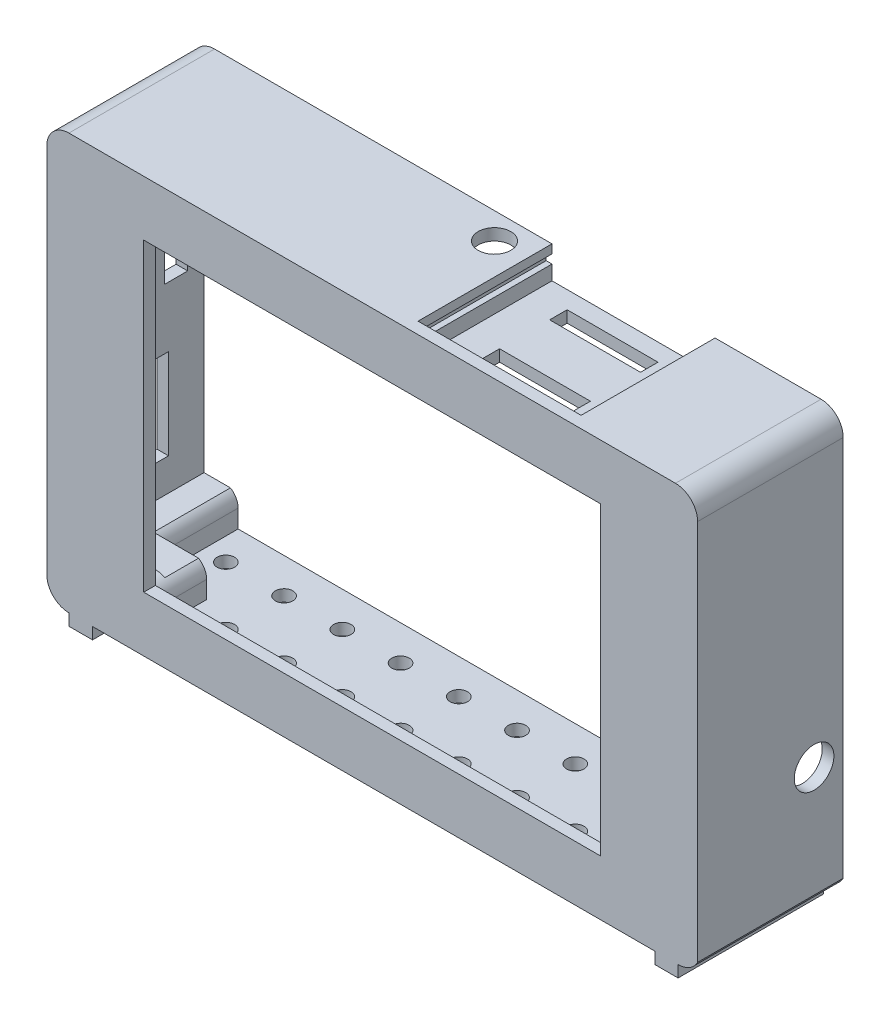
SolidWorks part; units mm, degrees
ref_plane "Спереди" through (0, 0, 0) normal (0, 0, 1) x (1, 0, 0)
ref_plane "Сверху" through (0, 0, 0) normal (0, 1, 0) x (1, 0, 0)
ref_plane "Справа" through (0, 0, 0) normal (1, 0, 0) x (0, 0, -1)
sketch "Skizze2" plane through (0, 0, 0) normal (0, 0, 1) x (1, 0, 0)
  line L12 (26.3261, 18.4704) -> (26.3261, 24.5704)
  line L13 (11.7261, 12.5004) -> (11.7261, 26.2004)
  line L14 (-51.1739, -27.8496) -> (45.3261, -27.8496)
  line L15 (-52.0078, 10.838) -> (-53.3578, 10.838)
  line L20 (-52.0078, 3.4844) -> (-53.3578, 3.4844)
  line L21 (-53.3578, 3.4844) -> (-53.3578, 3.338)
  line L22 (-53.3578, 3.338) -> (-52.0078, 3.338)
  line L23 (-52.0078, 3.338) -> (-52.0078, 3.4844)
  line L24 (-53.1739, 25.0904) -> (-53.1739, -25.8496)
  line L25 (45.3261, 27.0904) -> (-51.1739, 27.0904)
  line L26 (47.3261, -25.8496) -> (47.3261, 25.0904)
  line L27 (-39.7339, -26.5596) -> (38.7061, -26.5596)
  line L28 (-39.7339, 12.4004) -> (-39.7339, -26.5596)
  line L29 (38.7061, 25.8004) -> (-41.7339, 25.8004)
  line L30 (38.7061, -26.5596) -> (38.7061, 25.8004)
  circle A8 centre (44.1261, -24.6496) radius 1.6
  arc A9 (45.3261, -27.8496) -> (47.3261, -25.8496) centre (45.3261, -25.8496) ccw
  arc A10 (-53.1739, -25.8496) -> (-51.1739, -27.8496) centre (-51.1739, -25.8496) ccw
  circle A11 centre (-49.9739, -24.6496) radius 1.6
  arc A12 (-51.1739, 27.0904) -> (-53.1739, 25.0904) centre (-51.1739, 25.0904) ccw
  circle A13 centre (-49.9739, 23.8904) radius 1.6
  circle A14 centre (44.1261, 23.8904) radius 1.6
  arc A15 (47.3261, 25.0904) -> (45.3261, 27.0904) centre (45.3261, 25.0904) ccw
sketch "Skizze3" plane through (0, 0, 0) normal (0, 0, 1) x (1, 0, 0)
  line L0 (38.7061, -26.5596) -> (38.7061, 25.8004) construction
  line L1 (-39.7339, -26.5596) -> (38.7061, -26.5596) construction
  line L2 (-39.7339, 12.4004) -> (-39.7339, -26.5596) construction
  line L3 (38.7061, -26.5596) -> (38.7061, 25.8004)
  line L4 (-39.7339, -26.5596) -> (38.7061, -26.5596)
  line L5 (-39.7339, 12.4004) -> (-39.7339, -26.5596)
  line L6 (38.7061, 25.8004) -> (-39.7339, 25.8004)
  line L7 (38.7061, 25.8004) -> (-41.7339, 25.8004) construction
  line L8 (-39.7339, 25.8004) -> (-39.7339, 12.4004)
  line L9 (45.3261, 27.0904) -> (-51.1739, 27.0904) construction
  line L10 (-54.3739, 33.2904) -> (48.5261, 33.2904)
  line L11 (-54.3739, 33.2904) -> (-54.3739, -34.0496)
  line L12 (-54.3739, -34.0496) -> (48.5261, -34.0496)
  line L13 (48.5261, 33.2904) -> (48.5261, -34.0496)
  line L14 (-53.1739, 25.0904) -> (-53.1739, -25.8496) construction
  line L15 (47.3261, -25.8496) -> (47.3261, 25.0904) construction
  line L16 (-51.1739, -27.8496) -> (45.3261, -27.8496) construction
  circle A0 centre (-49.9739, 23.8904) radius 1.6 construction
  circle A1 centre (-49.9739, -24.6496) radius 1.6 construction
  circle A2 centre (44.1261, -24.6496) radius 1.6 construction
  circle A3 centre (44.1261, 23.8904) radius 1.6 construction
  circle A4 centre (-49.9739, 23.8904) radius 1.6
  circle A5 centre (-49.9739, -24.6496) radius 1.6
  circle A6 centre (44.1261, -24.6496) radius 1.6
  circle A7 centre (44.1261, 23.8904) radius 1.6
  dimension "D1" = 6.2
  dimension "D2" = 1.2
  dimension "D3" = 1.2
  dimension "D4" = 6.2
extrude "Aufsatz-Linear austragen1" add sketch "Skizze3" along normal blind 2
sketch "Skizze4" plane through (0, 0, 2) normal (0, 0, 1) x (1, 0, 0)
  line L1 (48.5261, 33.2904) -> (53.3661, 33.2904)
  line L2 (48.5261, 33.2904) -> (48.5261, -29.0496)
  line L3 (48.5261, -29.0496) -> (53.3661, -29.0496)
  line L4 (53.3661, 33.2904) -> (53.3661, -29.0496)
  dimension "D1" = 4.84
extrude "Aufsatz-Linear austragen2" add sketch "Skizze4" against normal blind 2
sketch "Skizze5" plane through (0, 0, 0) normal (0, 0, -1) x (-1, 0, 0)
  circle A0 centre (-44.1261, 23.8904) radius 1.6 construction
  circle A1 centre (-44.1261, -24.6496) radius 1.6 construction
  circle A2 centre (49.9739, -24.6496) radius 1.6 construction
  circle A3 centre (49.9739, 23.8904) radius 1.6 construction
  circle A4 centre (-44.1261, 23.8904) radius 1.6
  circle A5 centre (-44.1261, -24.6496) radius 1.6
  circle A6 centre (49.9739, -24.6496) radius 1.6
  circle A7 centre (49.9739, 23.8904) radius 1.6
extrude "Linear-Austragen-Dünn1" add sketch "Skizze5" along normal blind 4 thin thin type one direction wall 1.8
sketch "Skizze6" plane through (53.3661, 0, 0) normal (1, 0, 0) x (0, 0, -1)
  line L0 (0, -29.0496) -> (-2, -29.0496) construction
  line L1 (-2, 33.2904) -> (23, 33.2904)
  line L2 (-2, 33.2904) -> (-2, -29.0496)
  line L3 (-2, -29.0496) -> (23, -29.0496)
  line L4 (23, 33.2904) -> (23, -29.0496)
  dimension "D1" = 25
extrude "Aufsatz-Linear austragen3" add sketch "Skizze6" along normal blind 2
sketch "Skizze7" plane through (-54.3739, 0, 0) normal (-1, 0, 0) x (0, 0, 1)
  line L0 (2, 33.2904) -> (0, 33.2904) construction
  line L1 (2, -34.0496) -> (-23, -34.0496)
  line L2 (2, -34.0496) -> (2, 33.2904)
  line L3 (2, 33.2904) -> (-23, 33.2904)
  line L4 (-23, -34.0496) -> (-23, 33.2904)
  dimension "D1" = 25
extrude "Aufsatz-Linear austragen4" add sketch "Skizze7" along normal blind 2
sketch "Skizze8" plane through (0, 33.2904, 0) normal (0, 1, 0) x (1, 0, 0)
  line L1 (-56.3739, -2) -> (55.3661, -2)
  line L2 (-56.3739, -2) -> (-56.3739, 23)
  line L3 (-56.3739, 23) -> (55.3661, 23)
  line L4 (55.3661, -2) -> (55.3661, 23)
extrude "Aufsatz-Linear austragen5" add sketch "Skizze8" along normal blind 2
sketch "Skizze9" plane through (0, -34.0496, 0) normal (0, -1, 0) x (1, 0, 0)
  line L1 (55.3661, 2) -> (-56.3739, 2)
  line L2 (55.3661, 2) -> (55.3661, -23)
  line L3 (55.3661, -23) -> (-56.3739, -23)
  line L4 (-56.3739, 2) -> (-56.3739, -23)
extrude "Aufsatz-Linear austragen6" add sketch "Skizze9" along normal blind 2
fillet "Verrundung2" radius 3.8 4 edges at (55.3661, 35.2904, -10.5) (55.3661, -36.0496, -10.5) (-56.3739, -36.0496, -10.5) (-56.3739, 35.2904, -10.5)
sketch "Skizze10" plane through (-56.3739, 0, 0) normal (-1, 0, 0) x (0, 0, 1)
  line L0 (-23, 35.2904) -> (2, 35.2904) construction
  line L1 (-20.2, 11.7904) -> (-16.2, 11.7904)
  line L2 (-20.2, 11.7904) -> (-20.2, 2.7904)
  line L3 (-20.2, 2.7904) -> (-16.2, 2.7904)
  line L4 (-16.2, 11.7904) -> (-16.2, 2.7904)
  line L5 (-23, -29.0496) -> (-23, 33.2904) construction
  line L6 (-23, 31.4904) -> (-23, -32.2496) construction
  line L7 (-16.4, -8.5496) -> (-12.9, -8.5496)
  line L8 (-16.4, -8.5496) -> (-16.4, -22.0496)
  line L9 (-16.4, -22.0496) -> (-12.9, -22.0496)
  line L10 (-12.9, -8.5496) -> (-12.9, -22.0496)
  line L11 (2, -36.0496) -> (-23, -36.0496) construction
  dimension "D1" = 9
  dimension "D2" = 4
  dimension "D3" = 23.5
  dimension "D4" = 2.8
  dimension "D5" = 3.5
  dimension "D6" = 13.5
  dimension "D7" = 6.6
  dimension "D8" = 14
extrude "Schnitt-Linear austragen1" cut sketch "Skizze10" against normal blind 10
sketch "Skizze23" plane through (0, 0, 0) normal (0, 0, -1) x (-1, 0, 0)
  line L0 (-53.3661, 33.2904) -> (54.3739, 33.2904) construction
  line L1 (-33.3661, 33.2904) -> (-35.3661, 33.2904)
  line L2 (-33.3661, 33.2904) -> (-33.3661, 27.7904)
  line L3 (-33.3661, 27.7904) -> (-35.3661, 27.7904)
  line L4 (-35.3661, 33.2904) -> (-35.3661, 27.7904)
  line L5 (-55.3661, -29.0496) -> (-55.3661, 31.4904) construction
  line L6 (-3.3661, 33.2904) -> (-5.3661, 33.2904)
  line L7 (-3.3661, 33.2904) -> (-3.3661, 27.7904)
  line L8 (-3.3661, 27.7904) -> (-5.3661, 27.7904)
  line L9 (-5.3661, 33.2904) -> (-5.3661, 27.7904)
  line L10 (-33.3661, 27.7904) -> (-5.3661, 27.7904)
  line L11 (-33.3661, 27.7904) -> (-33.3661, 29.7904)
  line L12 (-33.3661, 29.7904) -> (-5.3661, 29.7904)
  line L13 (-5.3661, 27.7904) -> (-5.3661, 29.7904)
  line L14 (-45.3261, 27.0904) -> (51.1739, 27.0904) construction
  line M14 (54.3739, 33.2904) -> (-53.3661, 33.2904)
  dimension "D1" = 2
  dimension "D2" = 2
  dimension "D3" = 2
  dimension "D4" = 20
  dimension "D5" = 28
  dimension "D6" = 0.7
extrude "Aufsatz-Linear austragen13" add sketch "Skizze23" along normal blind 23 contours L12 L2 L10 L9 | L9 L8 L7 M14 | L4 L3 L2 M14 region at (34.3661, 30.5404, 0) region at (19.3661, 28.7904, 0) region at (4.3661, 30.5404, 0)
sketch "Skizze11" plane through (0, 35.2904, 0) normal (0, 1, 0) x (1, 0, 0)
  line L0 (45.3261, 0) -> (-51.1739, 0) construction
  line L1 (10.9661, 8.4) -> (26.5661, 8.4)
  line L2 (10.9661, 8.4) -> (10.9661, 5.4)
  line L3 (10.9661, 5.4) -> (26.5661, 5.4)
  line L4 (26.5661, 8.4) -> (26.5661, 5.4)
  line L5 (10.9661, 20) -> (26.5661, 20)
  line L6 (10.9661, 20) -> (10.9661, 17)
  line L7 (10.9661, 17) -> (26.5661, 17)
  line L8 (26.5661, 20) -> (26.5661, 17)
  line L10 (55.3661, 23) -> (55.3661, -2) construction
  dimension "D1" = 3
  dimension "D2" = 3
  dimension "D4" = 15.6
  dimension "D5" = 5.4
  dimension "D6" = 8.6
  dimension "D7" = 28.8
extrude "Schnitt-Linear austragen2" cut sketch "Skizze11" against normal blind 10
fillet "Verrundung3" radius 1 8 edges at (10.9661, 35.2904, -6.9) (18.7661, 35.2904, -8.4) (26.5661, 35.2904, -6.9) (10.9661, 35.2904, -18.5) (26.5661, 35.2904, -18.5) (18.7661, 35.2904, -20) (18.7661, 35.2904, -17) (18.7661, 35.2904, -5.4)
sketch "Skizze14" plane through (0, -36.0496, 0) normal (0, -1, 0) x (1, 0, 0)
  line L0 (55.3661, 2) -> (55.3661, -23) construction
  line L1 (-52.5739, -23) -> (52.0195, -23) construction
  circle A0 centre (45.3661, -17) radius 1.5
  circle A1 centre (35.3661, -17) radius 1.5
  circle A2 centre (25.3661, -17) radius 1.5
  circle A3 centre (15.3661, -17) radius 1.5
  circle A4 centre (5.3661, -17) radius 1.5
  circle A5 centre (-4.6339, -17) radius 1.5
  circle A6 centre (-14.6339, -17) radius 1.5
  circle A7 centre (-24.6339, -17) radius 1.5
  circle A8 centre (-34.6339, -17) radius 1.5
  circle A9 centre (-44.6339, -17) radius 1.5
  circle A10 centre (35.3661, -7) radius 1.5
  circle A11 centre (25.3661, -7) radius 1.5
  circle A12 centre (15.3661, -7) radius 1.5
  circle A13 centre (5.3661, -7) radius 1.5
  circle A14 centre (-4.6339, -7) radius 1.5
  circle A15 centre (-14.6339, -7) radius 1.5
  circle A16 centre (-24.6339, -7) radius 1.5
  circle A17 centre (-34.6339, -7) radius 1.5
  circle A18 centre (-44.6339, -7) radius 1.5
  circle A19 centre (45.3661, -7) radius 1.5
  dimension "D1" = 3
  dimension "D2" = 10
  dimension "D3" = 6
  dimension "D4" = 10
  dimension "D5" = 2
extrude "Schnitt-Linear austragen4" cut sketch "Skizze14" against normal blind 10
sketch "Skizze15" plane through (53.3661, 0, 0) normal (-1, 0, 0) x (0, 0, 1)
  line L1 (-23, -29.0496) -> (-23, 33.2904) construction
  line L2 (-23, -34.0496) -> (2, -34.0496) construction
  circle A0 centre (-18, -15.0496) radius 3.4
  dimension "D1" = 6.8
  dimension "D2" = 19
  dimension "D3" = 5
extrude "Schnitt-Linear austragen5" cut sketch "Skizze15" against normal blind 10
sketch "Skizze16" plane through (0, 0, 2) normal (0, 0, 1) x (1, 0, 0)
  circle A0 centre (44.1261, 23.8904) radius 1.6 construction
  circle A1 centre (44.1261, -24.6496) radius 1.6 construction
  circle A2 centre (-49.9739, -24.6496) radius 1.6 construction
  circle A3 centre (-49.9739, 23.8904) radius 1.6 construction
  circle A4 centre (44.1261, 23.8904) radius 1.6
  circle A5 centre (44.1261, -24.6496) radius 1.6
  circle A6 centre (-49.9739, -24.6496) radius 1.6
  circle A7 centre (-49.9739, 23.8904) radius 1.6
extrude "Aufsatz-Linear austragen7" add sketch "Skizze16" against normal blind 6
sketch "Skizze17" plane through (0, 0, -4) normal (0, 0, -1) x (-1, 0, 0)
  circle A0 centre (-44.1261, 23.8904) radius 1.05
  circle A1 centre (49.9739, 23.8904) radius 1.05
  circle A2 centre (49.9739, -24.6496) radius 1.05
  circle A3 centre (-44.1261, -24.6496) radius 1.05
  dimension "D1" = 2.1
extrude "Schnitt-Linear austragen6" cut sketch "Skizze17" against normal blind 5
fillet "Verrundung4" radius 2 2 edges at (-54.3739, 33.2904, -11.5) (53.3661, 33.2904, -11.5)
sketch "Skizze18" plane through (55.3661, 0, 0) normal (1, 0, 0) x (0, 0, -1)
  line L1 (23, -29.0496) -> (-2, -29.0496)
  line L2 (23, -29.0496) -> (23, -34.0496)
  line L3 (23, -34.0496) -> (-2, -34.0496)
  line L4 (-2, -29.0496) -> (-2, -34.0496)
extrude "Aufsatz-Linear austragen8" add sketch "Skizze18" against normal blind 2
sketch "Skizze19" plane through (0, 0, 2) normal (0, 0, 1) x (1, 0, 0)
  line L0 (53.3661, -34.0496) -> (48.5261, -34.0496) construction
  line L1 (48.5261, -34.0496) -> (48.5261, -29.0496) construction
  line L2 (48.5261, -29.0496) -> (53.3661, -29.0496) construction
  line L3 (53.3661, -29.0496) -> (53.3661, -34.0496) construction
  line L4 (53.3661, -34.0496) -> (48.5261, -34.0496)
  line L5 (48.5261, -34.0496) -> (48.5261, -29.0496)
  line L6 (48.5261, -29.0496) -> (53.3661, -29.0496)
  line L7 (53.3661, -29.0496) -> (53.3661, -34.0496)
extrude "Aufsatz-Linear austragen10" add sketch "Skizze19" against normal blind 2
sketch "Skizze20" plane through (0, 0, 0) normal (0, 0, -1) x (-1, 0, 0)
  line L0 (-44.1261, 32.0609) -> (-44.1261, -32.502) construction
  circle A0 centre (-44.1261, 30.2904) radius 2.85
  circle A1 centre (-44.1261, -31.0496) radius 2.85
  circle A2 centre (43.5739, -31.0496) radius 2.85
  circle A3 centre (43.5739, 30.2904) radius 2.85
  circle A4 centre (-44.1261, 23.8904) radius 3.4 construction
  circle A5 centre (-44.1261, -24.6496) radius 3.4 construction
  circle A6 centre (49.9739, -24.6496) radius 3.4 construction
  circle A7 centre (49.9739, -24.6496) radius 3.4 construction
  circle A8 centre (49.9739, 23.8904) radius 3.4 construction
  circle A9 centre (49.9739, 23.8904) radius 3.4 construction
  dimension "D1" = 5.7
  dimension "D2" = 0
  dimension "D3" = 6.4
  dimension "D4" = 0
  dimension "D5" = 6.4
  dimension "D6" = 6.4
  dimension "D7" = 6.4
  dimension "D8" = 6.4
  dimension "D9" = 6.4
extrude "Aufsatz-Linear austragen12" add sketch "Skizze20" along normal blind 9.8
sketch "Skizze21" plane through (0, 0, -9.8) normal (0, 0, -1) x (-1, 0, 0)
  circle A0 centre (43.5739, 30.2904) radius 1.05
  circle A1 centre (-44.1261, 30.2904) radius 1.05
  circle A2 centre (-44.1261, -31.0496) radius 1.05
  circle A3 centre (43.5739, -31.0496) radius 1.05
  dimension "D1" = 2.1
extrude "Schnitt-Linear austragen7" cut sketch "Skizze21" against normal blind 9
sketch "Skizze24" plane through (0, 0, -23) normal (0, 0, -1) x (-1, 0, 0)
  line L0 (-51.5661, 35.2904) -> (52.5739, 35.2904) construction
  line L1 (-33.3661, 33.2904) -> (-5.3661, 33.2904)
  line L2 (-33.3661, 33.2904) -> (-33.3661, 35.2904)
  line L3 (-33.3661, 35.2904) -> (-5.3661, 35.2904)
  line L4 (-5.3661, 33.2904) -> (-5.3661, 35.2904)
extrude "Schnitt-Linear austragen8" cut sketch "Skizze24" against normal blind 23
sketch "Skizze25" plane through (0, 0, -23) normal (0, 0, -1) x (-1, 0, 0)
  line L0 (-5.3661, 35.2904) -> (52.5739, 35.2904) construction
  line L1 (-4.3661, 33.7904) -> (-34.3661, 33.7904)
  line L2 (-4.3661, 33.7904) -> (-4.3661, 32.2904)
  line L3 (-4.3661, 32.2904) -> (-34.3661, 32.2904)
  line L4 (-34.3661, 33.7904) -> (-34.3661, 32.2904)
  line L5 (-5.3661, 35.2904) -> (-5.3661, 29.7904) construction
  line L6 (-33.3661, 35.2904) -> (-33.3661, 29.7904) construction
  dimension "D1" = 1.5
  dimension "D2" = 1
  dimension "D3" = 1.5
  dimension "D4" = 1
extrude "Schnitt-Linear austragen9" cut sketch "Skizze25" against normal blind 24
fillet "Verrundung5" radius 2 2 edges at (-54.3739, -34.0496, -11.5) (53.3661, -34.0496, -11.5)
sketch "Skizze26" plane through (0, 0, 0) normal (0, 0, -1) x (-1, 0, 0)
  line L0 (52.3739, -34.0496) -> (-51.3661, -34.0496) construction
  line L1 (54.3739, 31.2904) -> (54.3739, -32.0496) construction
  line L2 (54.3739, 31.2904) -> (54.3739, -32.0496) construction
  line L3 (-3.3661, 33.2904) -> (52.3739, 33.2904) construction
  line L4 (-53.3661, -32.0496) -> (-53.3661, 31.2904) construction
  line L5 (-51.3661, 33.2904) -> (-35.3661, 33.2904) construction
  circle A0 centre (-50.2661, -30.9496) radius 2.75
  circle A1 centre (-50.2661, 30.1904) radius 2.75
  circle A2 centre (51.2739, 30.1904) radius 2.75
  circle A3 centre (51.2739, -30.9496) radius 2.75
  dimension "D1" = 3.1
  dimension "D2" = 3.1
  dimension "D3" = 5.5
  dimension "D4" = 3.1
  dimension "D5" = 3.1
  dimension "D6" = 3.1
  dimension "D7" = 3.1
  dimension "D8" = 3.1
  dimension "D9" = 3.1
extrude "Aufsatz-Linear austragen14" add sketch "Skizze26" along normal blind 23
sketch "Skizze27" plane through (0, 0, -23) normal (0, 0, -1) x (-1, 0, 0)
  line L0 (-47.5161, 30.1904) -> (-47.5161, 33.2904)
  line L1 (-51.3661, 33.2904) -> (-35.3661, 33.2904) construction
  line L2 (-50.2661, 27.4404) -> (-53.3661, 27.4404)
  line L3 (-53.3661, -32.0496) -> (-53.3661, 31.2904) construction
  line L4 (-53.3661, 27.4404) -> (-53.3661, 31.2904)
  line L5 (-47.5161, 33.2904) -> (-51.3661, 33.2904)
  line L6 (48.5239, 30.1904) -> (48.5239, 33.2904)
  line L7 (-3.3661, 33.2904) -> (52.3739, 33.2904) construction
  line L8 (48.5239, 33.2904) -> (52.3739, 33.2904)
  line L9 (54.3739, 31.2904) -> (54.3739, 30.1904)
  line L10 (54.3739, 31.2904) -> (54.3739, -32.0496) construction
  line L11 (54.3739, 30.1904) -> (54.3739, 27.4404)
  line L12 (54.3739, 27.4404) -> (51.2739, 27.4404)
  line L13 (51.2739, -28.1996) -> (54.3739, -28.1996)
  line L14 (54.3739, -28.1996) -> (54.3739, -32.0496)
  line L15 (48.5239, -30.9496) -> (48.5239, -34.0496)
  line L16 (52.3739, -34.0496) -> (-51.3661, -34.0496) construction
  line L17 (48.5239, -34.0496) -> (52.3739, -34.0496)
  line L18 (-50.2661, -28.1996) -> (-53.3661, -28.1996)
  line L19 (-53.3661, -28.1996) -> (-53.3661, -32.0496)
  line L20 (-47.5161, -30.9496) -> (-47.5161, -34.0496)
  line L21 (-47.5161, -34.0496) -> (-51.3661, -34.0496)
  circle A0 centre (-50.2661, 30.1904) radius 2.75 construction
  circle A1 centre (-50.2661, 30.1904) radius 2.75
  arc A2 (-51.3661, 33.2904) -> (-53.3661, 31.2904) centre (-51.3661, 31.2904) ccw construction
  arc A3 (-51.3661, 33.2904) -> (-53.3661, 31.2904) centre (-51.3661, 31.2904) ccw
  circle A4 centre (-50.2661, -30.9496) radius 2.75 construction
  circle A5 centre (-50.2661, -30.9496) radius 2.75
  arc A6 (-53.3661, -32.0496) -> (-51.3661, -34.0496) centre (-51.3661, -32.0496) ccw construction
  arc A7 (-53.3661, -32.0496) -> (-51.3661, -34.0496) centre (-51.3661, -32.0496) ccw
  arc A8 (52.3739, -34.0496) -> (54.3739, -32.0496) centre (52.3739, -32.0496) ccw construction
  circle A9 centre (51.2739, -30.9496) radius 2.75 construction
  arc A10 (52.3739, -34.0496) -> (54.3739, -32.0496) centre (52.3739, -32.0496) ccw
  circle A11 centre (51.2739, -30.9496) radius 2.75
  circle A12 centre (51.2739, 30.1904) radius 2.75 construction
  arc A13 (54.3739, 31.2904) -> (52.3739, 33.2904) centre (52.3739, 31.2904) ccw construction
  circle A14 centre (51.2739, 30.1904) radius 2.75
  arc A15 (54.3739, 31.2904) -> (52.3739, 33.2904) centre (52.3739, 31.2904) ccw
  circle M1 centre (-50.2661, 30.1904) radius 2.75
extrude "Aufsatz-Linear austragen15" add sketch "Skizze27" against normal blind 23 contours L5 A3 L4 L2 L0 M1 | L19 A7 L21 L20 A5 L18 | A11 L15 L17 A10 L14 L13 | L9 A15 L8 L6 A14 L12 L11 region at (52.2692, 32.1935, -23) region at (-48.6066, 31.7404, -23) region at (-52.8239, -28.2823, -23) region at (52.2692, -32.9526, -23)
sketch "Skizze28" plane through (0, 0, -23) normal (0, 0, -1) x (-1, 0, 0)
  circle A0 centre (-50.2661, 30.1904) radius 1.05
  circle A1 centre (-50.2661, -30.9496) radius 1.05
  circle A2 centre (51.2739, -30.9496) radius 1.05
  circle A3 centre (51.2739, 30.1904) radius 1.05
  dimension "D1" = 2.1
extrude "Schnitt-Linear austragen10" cut sketch "Skizze28" against normal blind 20
sketch "Skizze29" plane through (0, 0, -4) normal (0, 0, -1) x (-1, 0, 0)
  line L0 (-40.7261, 23.8904) -> (-40.7261, 33.3073)
  line L1 (-40.7261, 33.3073) -> (-47.5261, 33.3073)
  line L2 (-47.5261, 33.3073) -> (-47.5261, 23.8904)
  line L3 (-40.7261, -24.6496) -> (-40.7261, -34.4378)
  line L4 (-47.5261, -24.6496) -> (-47.5261, -34.4378)
  line L5 (-47.5261, -34.4378) -> (-40.7261, -34.4378)
  line L6 (46.5739, -24.6496) -> (46.5739, -34.8237)
  line L7 (46.5739, -34.8237) -> (50.6053, -34.8237)
  line L8 (50.6053, -34.8237) -> (50.6053, -30.793)
  line L9 (50.6053, -30.793) -> (52.3944, -29.1539)
  line L10 (52.3944, -29.1539) -> (56.3554, -29.1539)
  line L11 (56.3554, -29.1539) -> (56.3554, -24.6496)
  line L12 (49.9739, -21.2496) -> (56.1975, -21.2496)
  line L13 (56.1975, -21.2496) -> (56.3554, -24.6496)
  line L14 (49.9739, 20.4904) -> (54.9324, 20.4904)
  line L15 (54.9324, 20.4904) -> (54.9324, 31.3117)
  line L16 (54.9324, 31.3117) -> (50.6053, 31.3117)
  line L17 (50.6053, 31.3117) -> (49.1258, 33.0872)
  line L18 (49.1258, 33.0872) -> (49.1258, 34.6337)
  line L19 (49.1258, 34.6337) -> (46.5739, 34.6337)
  line L20 (46.5739, 34.6337) -> (46.5739, 23.8904)
  circle A0 centre (-44.1261, 23.8904) radius 3.4 construction
  circle A1 centre (-44.1261, 23.8904) radius 3.4
  circle A2 centre (-44.1261, -24.6496) radius 3.4 construction
  circle A3 centre (-44.1261, -24.6496) radius 3.4
  circle A4 centre (49.9739, -24.6496) radius 3.4 construction
  circle A5 centre (49.9739, -24.6496) radius 3.4
  circle A6 centre (49.9739, 23.8904) radius 3.4 construction
  circle A7 centre (49.9739, 23.8904) radius 3.4
  circle M2 centre (-44.1261, 23.8904) radius 3.4
extrude "Aufsatz-Linear austragen16" add sketch "Skizze29" against normal blind 4 contours L1 L2 L0 M2 | A3 L4 L5 L3 | A5 L6 L7 L8 L9 L10 L11 | A7 L14 L15 L16 L17 L18 L19 L20 region at (44.1261, 29.8914, -4) region at (44.1261, -30.8384, -4) region at (-51.4165, -28.2455, -4) region at (-50.927, 28.3813, -4)
sketch "Skizze31" plane through (0, 0, -9.8) normal (0, 0, -1) x (-1, 0, 0)
  line L0 (43.5739, 27.4404) -> (55.5967, 27.4404)
  line L1 (55.5967, 27.4404) -> (55.5967, 29.4449)
  line L2 (55.5967, 29.4449) -> (51.3277, 29.4449)
  line L3 (51.3277, 29.4449) -> (49.5853, 30.637)
  line L4 (49.5853, 30.637) -> (49.5853, 35.0698)
  line L5 (49.5853, 35.0698) -> (40.7239, 35.0698)
  line L6 (40.7239, 35.0698) -> (40.7239, 30.2904)
  line L7 (-41.2761, 30.2904) -> (-41.2761, 34.0252)
  line L8 (-41.2761, 34.0252) -> (-47.8148, 34.0252)
  line L9 (-47.8148, 34.0252) -> (-47.8148, 31.1599)
  line L10 (-44.1261, 27.4404) -> (-50.2661, 27.4404)
  line L11 (-50.2661, 27.4404) -> (-47.8148, 31.1599)
  line L12 (-44.1261, -28.1996) -> (-50.2661, -28.1996)
  line L13 (-50.2661, -28.1996) -> (-48.2842, -30.5448)
  line L14 (-48.2842, -30.5448) -> (-48.2842, -34.3449)
  line L15 (-48.2842, -34.3449) -> (-41.5253, -34.3449)
  line L16 (-41.2761, -34.3449) -> (-41.2761, -31.0496)
  line L17 (40.7239, -31.0496) -> (40.7239, -34.6268)
  line L18 (40.7239, -34.6268) -> (49.0901, -34.6268)
  line L19 (49.0901, -34.6268) -> (49.0901, -31.0496)
  line L20 (49.0901, -31.0496) -> (51.3277, -28.6957)
  line L21 (51.3277, -28.6957) -> (51.2739, -28.1996)
  line L22 (51.2739, -28.1996) -> (43.5739, -28.1996)
  line L23 (-41.5253, -34.3449) -> (-41.2761, -34.3449)
  circle A0 centre (43.5739, 30.2904) radius 2.85 construction
  circle A1 centre (43.5739, 30.2904) radius 2.85
  circle A2 centre (-44.1261, 30.2904) radius 2.85 construction
  circle A3 centre (-44.1261, 30.2904) radius 2.85
  circle A4 centre (-44.1261, -31.0496) radius 2.85 construction
  circle A5 centre (-44.1261, -31.0496) radius 2.85
  circle A6 centre (43.5739, -31.0496) radius 2.85 construction
  circle A7 centre (43.5739, -31.0496) radius 2.85
  circle M2 centre (43.5739, 30.2904) radius 2.85
extrude "Aufsatz-Linear austragen17" add sketch "Skizze31" against normal blind 10 contours L5 L6 L0 L1 L2 L3 L4 M2 | A3 L7 L8 L9 | A7 L17 L18 L19 L20 L21 L22 | A5 L12 L13 L14 L15 L23 L16 region at (-47.8075, 31.1578, -9.8) region at (46.2202, 32.3845, -9.8) region at (46.2184, -33.1418, -9.8) region at (-46.8573, -31.5927, -9.8)
sketch "Skizze34" plane through (0, 35.2904, 0) normal (0, 1, 0) x (1, 0, 0)
  circle A0 centre (0, 18.4912) radius 2.8
  dimension "D1" = 5.6
extrude "Schnitt-Linear austragen11" cut sketch "Skizze34" against normal blind 10
sketch "Skizze35" plane through (0, -36.0496, 0) normal (0, -1, 0) x (1, 0, 0)
  line L0 (-52.5739, -23) -> (52.0195, -23) construction
  line L1 (-52.5739, 2) -> (-48.5239, 2)
  line L2 (-52.5739, 2) -> (-52.5739, -23)
  line L3 (-52.5739, -23) -> (-48.5239, -23)
  line L4 (-48.5239, 2) -> (-48.5239, -23)
  line L5 (52.0195, 2) -> (48.0195, 2)
  line L6 (52.0195, 2) -> (52.0195, -23)
  line L7 (52.0195, -23) -> (48.0195, -23)
  line L8 (48.0195, 2) -> (48.0195, -23)
  dimension "D1" = 4
extrude "Aufsatz-Linear austragen18" add sketch "Skizze35" along normal blind 2
sketch "Skizze36" plane through (0, 27.4404, 0) normal (0, -1, 0) x (1, 0, 0)
  line L0 (50.2661, -23) -> (53.3661, -23) construction
  line L1 (47.5261, -4) -> (47.5261, 0) construction
  line L2 (44.1261, -4) -> (47.5261, -4) construction
  line L3 (44.1261, -9.8) -> (50.2661, -9.8) construction
  line L4 (47.5261, 0) -> (53.3661, 0) construction
  line L5 (53.3661, 0) -> (53.3661, -23) construction
  line L6 (50.2661, -23) -> (53.3661, -23)
  line L7 (47.5261, -4) -> (47.5261, 0)
  line L8 (44.1261, -4) -> (47.5261, -4)
  line L9 (44.1261, -9.8) -> (50.2661, -9.8)
  line L10 (47.5261, 0) -> (53.3661, 0)
  line L11 (53.3661, 0) -> (53.3661, -23)
  line L12 (50.2661, -23) -> (49.0632, -23)
  line L13 (49.0632, -23) -> (49.0632, -9.8)
  line L14 (44.1261, -9.8) -> (42.4266, -9.8)
  line L15 (42.4266, -9.8) -> (42.6291, -4)
  line L16 (42.6291, -4) -> (44.1261, -4)
  line L17 (-54.3739, -23) -> (-51.2739, -23) construction
  line L18 (-43.5739, -9.8) -> (-51.2739, -9.8) construction
  line L19 (-54.3739, -4) -> (-54.3739, -23) construction
  line L20 (-46.5739, 0) -> (-46.5739, -4) construction
  line L21 (-46.5739, -4) -> (-54.3739, -4) construction
  line L22 (-46.5739, 0) -> (-43.5739, 0) construction
  line L23 (-54.3739, -23) -> (-51.2739, -23)
  line L24 (-43.5739, -9.8) -> (-51.2739, -9.8)
  line L25 (-54.3739, -4) -> (-54.3739, -23)
  line L26 (-46.5739, 0) -> (-46.5739, -4)
  line L27 (-46.5739, -4) -> (-54.3739, -4)
  line L28 (-46.5739, 0) -> (-43.5739, 0)
  line L29 (-51.2739, -23) -> (-49.2005, -23)
  line L30 (-49.2005, -23) -> (-49.2005, -9.8)
  line L31 (-43.5739, -9.8) -> (-41.6091, -9.8)
  line L32 (-41.6091, -9.8) -> (-41.6091, 0)
  line L33 (-41.6091, 0) -> (-43.5739, 0)
extrude "Schnitt-Linear austragen13" cut sketch "Skizze36" against normal blind 0.4 contours L32 L33 L28 L26 L27 L25 L23 L29 L30 L24 L31 | L14 L7 L8 L9 L10 L11 L12 L13 | L13 L12 L14 L9 | L16 L15 L14 L12 region at (49.6528, 27.4404, -9.8764) region at (-54.1108, 27.4404, -13.5)
sketch "Skizze38" plane through (0, -28.1996, 0) normal (0, 1, 0) x (1, 0, 0)
  line L1 (-54.3739, 4) -> (53.3661, 4)
  line L2 (-54.3739, 4) -> (-54.3739, 23)
  line L3 (-54.3739, 23) -> (53.3661, 23)
  line L4 (53.3661, 4) -> (53.3661, 23)
extrude "Schnitt-Linear austragen14" cut sketch "Skizze38" against normal blind 0.4
sketch "Skizze39" plane through (-56.3739, 0, 0) normal (-1, 0, 0) x (0, 0, 1)
  line L1 (-16.4, -22.0496) -> (-12.9, -22.0496) construction
  line L2 (-16.9, -23.0496) -> (-12.4, -23.0496)
  line L3 (-16.9, -23.0496) -> (-16.9, -7.5496)
  line L4 (-16.9, -7.5496) -> (-12.4, -7.5496)
  line L6 (-12.4, -23.0496) -> (-12.4, -7.5496)
  line L7 (-12.9, -22.0496) -> (-12.9, -8.5496) construction
  line L8 (-12.9, -8.5496) -> (-16.4, -8.5496) construction
  line L9 (-16.4, -8.5496) -> (-16.4, -22.0496) construction
  dimension "D1" = 1
  dimension "D2" = 0.5
  dimension "D3" = 1
  dimension "D4" = 0.5
extrude "Schnitt-Linear austragen15" cut sketch "Skizze39" against normal blind 2
equation "\"8ьь\"=0.00799654"
